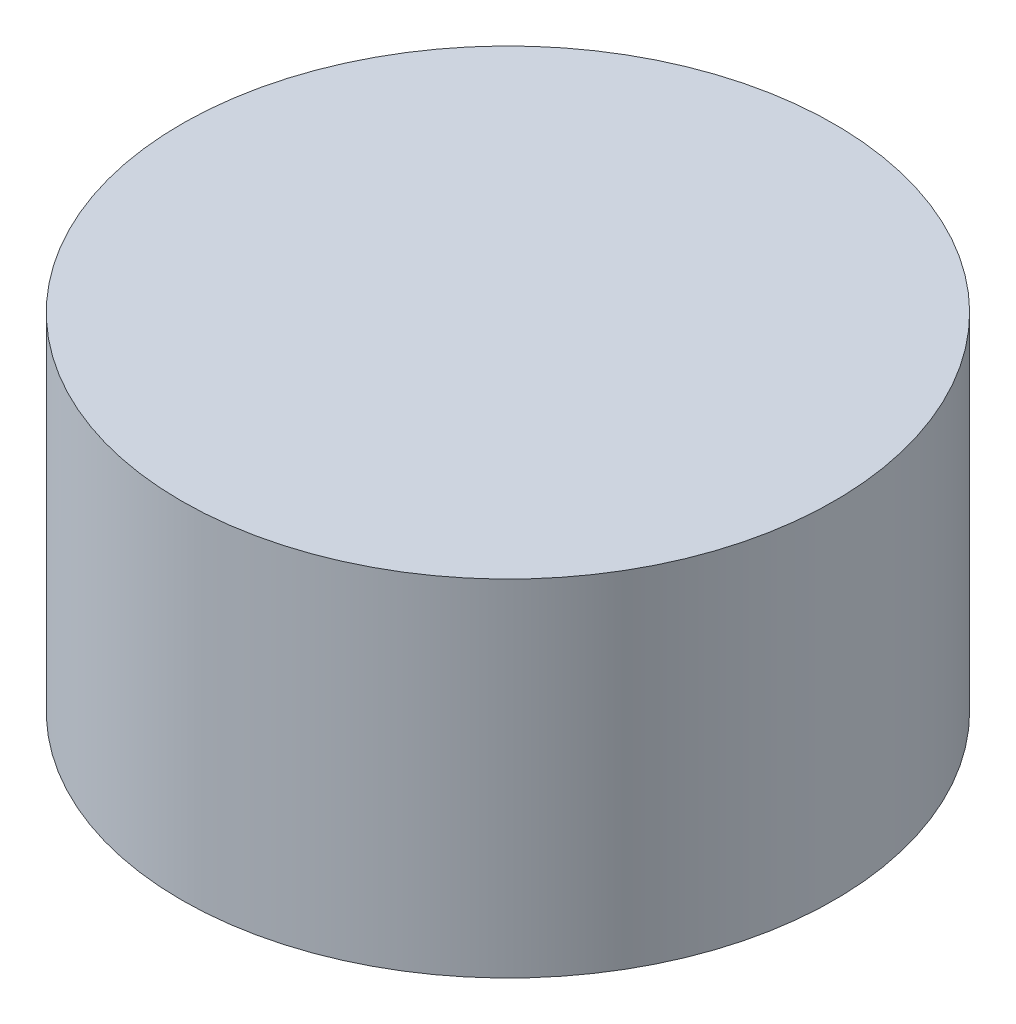
SolidWorks part; units mm, degrees
ref_plane "Front Plane" through (0, 0, 0) normal (0, 0, 1) x (1, 0, 0)
ref_plane "Top Plane" through (0, 0, 0) normal (0, 1, 0) x (1, 0, 0)
ref_plane "Right Plane" through (0, 0, 0) normal (1, 0, 0) x (0, 0, -1)
sketch "Sketch1" plane through (0, 0, 0) normal (0, 1, 0) x (1, 0, 0)
  circle A0 centre (0, 0) radius 30
  dimension "D1" = 60
extrude "Boss-Extrude1" add sketch "Sketch1" along normal blind 31.75
sketch "Sketch3" plane through (0, 0, 0) normal (0, -1, 0) x (1, 0, 0)
  line L0 (3.2928, 18) -> (-5.3006, 18) construction
  line L1 (2.5019, 18) -> (-2.5019, 18)
  arc A0 (-2.5019, 18) -> (2.5019, 18) centre (0, 18) ccw
  point P10 (0, 0)
  dimension "D1" = 18
revolve "Cut-Revolve7" cut sketch "Sketch3" angle 360 about L0
pattern_circular "CirPattern1" count 3 over 360 about axis through (0, 0, 0) along (0, 1, 0) of "Cut-Revolve7"
sketch "Sketch5" plane through (0, 0, 0) normal (0, -1, 0) x (1, 0, 0)
  line L0 (-9, 0) -> (-9, -15)
  line L1 (-9, -15) -> (-18, -24)
  line L2 (0, -1.8595) -> (0, 3.43) construction
  line L3 (9, 0) -> (9, -15)
  line L4 (9, -15) -> (18, -24)
  circle A0 centre (0, 0) radius 9
  circle A3 centre (0, 0) radius 30 construction
  circle A4 centre (0, 0) radius 30
  circle M5 centre (0, 0) radius 30
  dimension "D1" = 18
  dimension "D2" = 15
  dimension "D3" = 135
extrude "Cut-Extrude1" cut sketch "Sketch5" against normal blind 22.225 contours A0 L0 L1 L4 L3 M5 | A0 region at (0, 0, -19.3032) region at (0, 0, 0)
